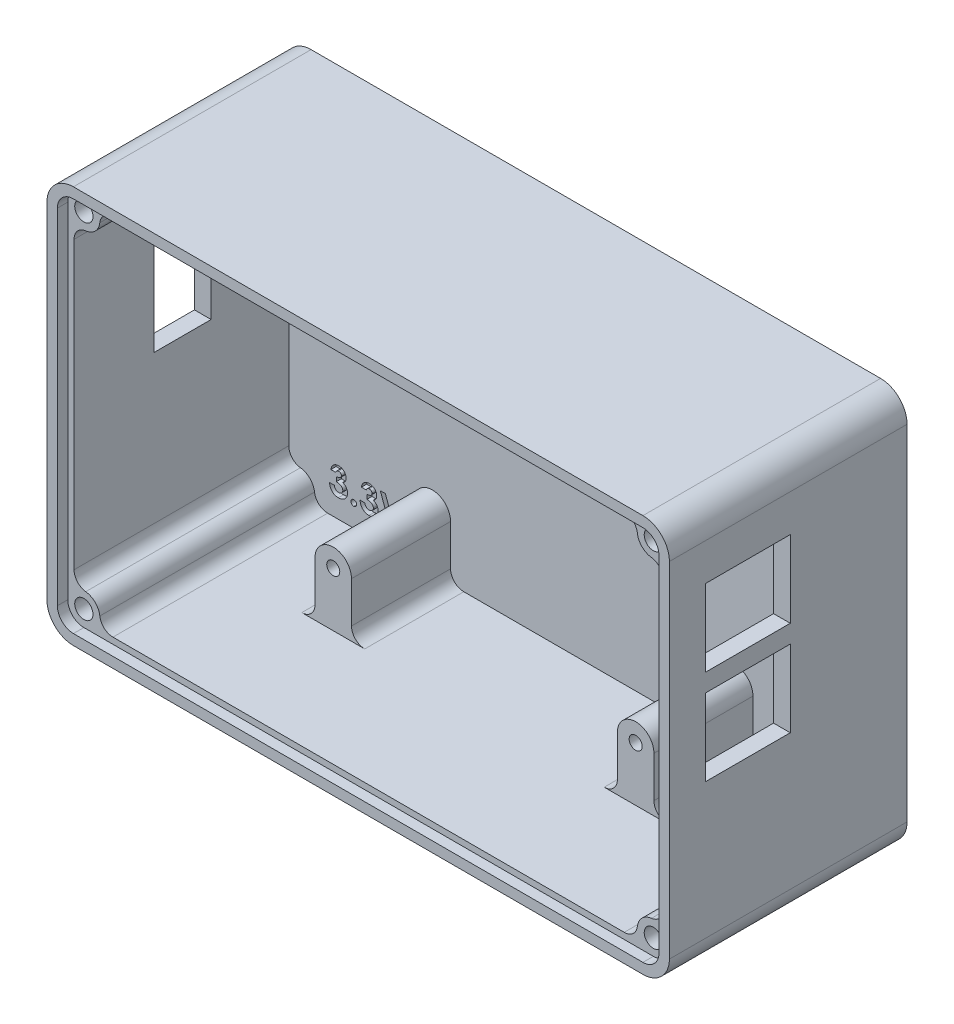
SolidWorks part; units mm, degrees
material "ABS"
ref_plane "Front Plane" through (0, 0, 0) normal (0, 0, 1) x (1, 0, 0)
ref_plane "Top Plane" through (0, 0, 0) normal (0, 1, 0) x (1, 0, 0)
ref_plane "Right Plane" through (0, 0, 0) normal (1, 0, 0) x (0, 0, -1)
sketch "OdroidOutline" plane through (0, 0, 0) normal (0, 0, 1) x (1, 0, 0)
  line L1 (-42.5, 28) -> (42.5, 28)
  line L2 (-42.5, 28) -> (-42.5, -28)
  line L3 (-42.5, -28) -> (42.5, -28)
  line L4 (42.5, 28) -> (42.5, -28)
  line L5 (-42.5, 28) -> (42.5, -28) construction
  line L6 (-42.5, -28) -> (42.5, 28) construction
  line L7 (19, -24.5) -> (-39, -24.5) construction
  line L8 (19, -24.5) -> (19, 24.5) construction
  line L9 (19, 24.5) -> (-39, 24.5) construction
  line L10 (-39, -24.5) -> (-39, 24.5) construction
  line L11 (44, -25.54) -> (22.3, -25.54)
  line L12 (44, -25.54) -> (44, -9.96)
  line L13 (44, -9.96) -> (22.3, -9.96)
  line L14 (22.3, -25.54) -> (22.3, -9.96)
  line L15 (44, -5.565) -> (26.44, -5.565)
  line L16 (44, -5.565) -> (44, 7.565)
  line L17 (44, 7.565) -> (26.44, 7.565)
  line L18 (26.44, -5.565) -> (26.44, 7.565)
  line L19 (44, 12.435) -> (26.44, 12.435)
  line L20 (44, 12.435) -> (44, 25.565)
  line L21 (44, 25.565) -> (26.44, 25.565)
  line L22 (26.44, 12.435) -> (26.44, 25.565)
  circle A0 centre (19, -24.5) radius 1.25
  circle A1 centre (-39, -24.5) radius 1.25
  circle A2 centre (-39, 24.5) radius 1.25
  circle A3 centre (19, 24.5) radius 1.25
  point P0 (0, 0)
  point P26 (44, -17.75)
  point P27 (44, 1)
  point P28 (44, 19)
  dimension "D7" = 2.5
  dimension "D1" = 85
  dimension "D2" = 56
  dimension "D3" = 58
  dimension "D4" = 49
  dimension "D5" = 3.5
  dimension "D6" = 3.5
  dimension "D8" = 10.25
  dimension "D9" = 29
  dimension "D10" = 47
  dimension "D11" = 15.58
  dimension "D12" = 21.7
  dimension "D13" = 13.13
  dimension "D14" = 17.56
  dimension "D15" = 1.5
sketch "BatteryOutline" plane through (0, 0, 0) normal (0, 0, 1) x (1, 0, 0)
  line L0 (6.5632, -21.195) -> (6.5632, 21.195) construction
  line L2 (-42.5, 0) -> (6.5632, 0) construction
  line L3 (-42.5, 28) -> (-42.5, -28) construction
  line L4 (6.5632, 21.195) -> (6.5632, 24.5) construction
  line L7 (44.3132, -30.5) -> (-31.1868, -30.5)
  line L8 (44.3132, -30.5) -> (44.3132, 30.5)
  line L9 (44.3132, 30.5) -> (-31.1868, 30.5)
  line L10 (-31.1868, -30.5) -> (-31.1868, 30.5)
  line L11 (44.3132, -30.5) -> (-31.1868, 30.5) construction
  line L12 (44.3132, 30.5) -> (-31.1868, -30.5) construction
  circle A0 centre (6.5632, 21.195) radius 1.75
  circle A1 centre (6.5632, -21.195) radius 1.75
  point P3 (6.5632, 0)
  dimension "D2" = 3.5
  dimension "D1" = 42.39
  dimension "D3" = 75.5
  dimension "D4" = 61
sketch "Sketch4" plane through (0, 0, 0) normal (0, 0, 1) x (1, 0, 0)
  line L0 (53.5, 0) -> (-53.5, 0) construction
  line L1 (53.5, -15) -> (53.5, 15) construction
  line L2 (-53.5, -15) -> (-53.5, 15) construction
  circle A0 centre (53.5, 15) radius 1.75
  circle A1 centre (-53.5, 15) radius 1.75
  circle A2 centre (-53.5, -15) radius 1.75
  circle A3 centre (53.5, -15) radius 1.75
  point P5 (0, 0)
  point P6 (53.5, 0)
  point P9 (-53.5, 0)
  dimension "D1" = 3.5
  dimension "D2" = 30
  dimension "D3" = 107
sketch "Sketch5" plane through (0, 0, 0) normal (0, 0, 1) x (1, 0, 0)
  line L0 (44.5696, 34.9) -> (-64.6504, 34.9)
  line L1 (44.5696, -38.1) -> (-64.6504, -38.1)
  line L2 (49.6496, -33.02) -> (49.6496, 33.02)
  line L3 (44.5696, 38.1) -> (-64.6504, 38.1)
  line L4 (-69.7304, -33.02) -> (-69.7304, 33.02)
  line L5 (49.6496, -38.1) -> (-69.7304, 38.1) construction
  line L6 (49.6496, 38.1) -> (-69.7304, -38.1) construction
  line L7 (-66.5304, -33.02) -> (-66.5304, 33.02)
  line L8 (44.5696, -34.9) -> (-64.6504, -34.9)
  line L9 (46.4496, -33.02) -> (46.4496, 33.02)
  arc A0 (-64.6504, -38.1) -> (-69.7304, -33.02) centre (-64.6504, -33.02) cw
  arc A1 (44.5696, -38.1) -> (49.6496, -33.02) centre (44.5696, -33.02) ccw
  arc A2 (49.6496, 33.02) -> (44.5696, 38.1) centre (44.5696, 33.02) ccw
  arc A3 (-64.6504, 38.1) -> (-69.7304, 33.02) centre (-64.6504, 33.02) ccw
  arc A4 (-64.6504, 34.9) -> (-66.5304, 33.02) centre (-64.6504, 33.02) ccw
  arc A5 (-64.6504, -34.9) -> (-66.5304, -33.02) centre (-64.6504, -33.02) cw
  arc A6 (44.5696, -34.9) -> (46.4496, -33.02) centre (44.5696, -33.02) ccw
  arc A7 (46.4496, 33.02) -> (44.5696, 34.9) centre (44.5696, 33.02) ccw
  dimension "D6" = 5.08
  dimension "D1" = 76.2
  dimension "D2" = 119.38
  dimension "D3" = 3.2
extrude "Enclosure Base" add sketch "Sketch5" along normal blind 2.4 contours L3 A3 L4 A0 L1 A1 L2 A2
extrude "Enclosure Wall" add sketch "Sketch5<3>" along normal blind 43.18 from surface contours L3 A3 L4 A0 L1 A1 L2 A2 A7 L9 A6 L8 A5 L7 A4 L0 region at (-10.0404, -36.6837, 0) starting at face at (-10.0404, 0, 2.4)
sketch "Sketch5<3>" plane through (0, 0, 0) normal (0, 0, 1) x (1, 0, 0) same geometry as "Sketch5"
sketch "Sketch6" plane through (0, 0, 2.4) normal (0, 0, 1) x (1, 0, 0)
  line L5 (-10, -24.5) -> (-10, 29.9225) construction
  line L6 (19, -24.5) -> (-39, -24.5) construction
  line L7 (-39, 0) -> (30.934, 0) construction
  line L8 (-39, -24.5) -> (-39, 24.5) construction
  line L19 (-35.5, 24.5) -> (-35.5, 34.9)
  line L20 (-64.6504, 34.9) -> (44.5696, 34.9) construction
  line L21 (-35.5, 34.9) -> (-42.5, 34.9)
  line L22 (-64.6504, 34.9) -> (44.5696, 34.9) construction
  line L23 (-42.5, 34.9) -> (-42.5, 24.5)
  line L24 (-42.5, 28) -> (42.5, 28) construction
  line L25 (15.5, 24.5) -> (15.5, 34.9)
  line L26 (15.5, 34.9) -> (22.5, 34.9)
  line L27 (22.5, 34.9) -> (22.5, 24.5)
  line L28 (15.5, -24.5) -> (15.5, -34.9)
  line L29 (15.5, -34.9) -> (22.5, -34.9)
  line L30 (22.5, -34.9) -> (22.5, -24.5)
  line L31 (-42.5, -34.9) -> (-42.5, -24.5)
  line L32 (-35.5, -34.9) -> (-42.5, -34.9)
  line L33 (-35.5, -24.5) -> (-35.5, -34.9)
  circle A4 centre (-39, 24.5) radius 1.25 construction
  circle A5 centre (-39, -24.5) radius 1.25 construction
  circle A6 centre (19, 24.5) radius 1.25 construction
  circle A7 centre (19, -24.5) radius 1.25 construction
  circle A8 centre (-39, 24.5) radius 1.25
  circle A9 centre (-39, -24.5) radius 1.25
  circle A10 centre (19, 24.5) radius 1.25
  circle A11 centre (19, -24.5) radius 1.25
  arc A12 (-42.5, 24.5) -> (-35.5, 24.5) centre (-39, 24.5) ccw
  arc A13 (15.5, 24.5) -> (22.5, 24.5) centre (19, 24.5) ccw
  arc A14 (-35.5, 24.5) -> (-42.5, 24.5) centre (-39, 24.5) ccw construction
  arc A15 (22.5, 24.5) -> (15.5, 24.5) centre (19, 24.5) ccw construction
  arc A16 (15.5, -24.5) -> (22.5, -24.5) centre (19, -24.5) cw
  arc A17 (-42.5, -24.5) -> (-35.5, -24.5) centre (-39, -24.5) cw
extrude "Odroid Mount Spacer" add sketch "Sketch6" along normal blind 19
sketch "Sketch7" plane through (-69.7304, 0, 0) normal (-1, 0, 0) x (0, 0, 1)
  line L1 (28.29, 0.9747) -> (17.29, 0.9747)
  line L2 (28.29, 0.9747) -> (28.29, 26.9747)
  line L3 (28.29, 26.9747) -> (17.29, 26.9747)
  line L4 (17.29, 0.9747) -> (17.29, 26.9747)
  line L5 (28.29, 0.9747) -> (17.29, 26.9747) construction
  line L6 (28.29, 26.9747) -> (17.29, 0.9747) construction
  line L7 (22.79, 33.02) -> (22.79, 13.9747) construction
  line L8 (45.58, 33.02) -> (0, 33.02) construction
  point P0 (22.79, 13.9747)
  dimension "D1" = 26
  dimension "D2" = 11
extrude "Power Switch Hole" cut sketch "Sketch7" against normal blind 7.112
sketch "Sketch8" plane through (0, 0, 2.4) normal (0, 0, 1) x (1, 0, 0)
  line L0 (-58.9104, 25.9564) -> (-58.9104, -31.1936) construction
  line L1 (-66.5304, -33.02) -> (-66.5304, 33.02) construction
  line L4 (49.6496, 38.1) -> (-69.7304, -38.1) construction
  text T0 "<b>3.3V</b>" font "Century Gothic" height 5.08
  text T1 "<b>5.0V</b>" font "Century Gothic" height 5.08
  text T2 "<b>Vin</b>" font "Century Gothic" height 3.175
  dimension "D1" = 57.15
  dimension "D2" = 7.62
extrude "Labeling" cut sketch "Sketch8" against normal blind 1
sketch "Sketch9" plane through (0, 0, 45.58) normal (0, 0, 1) x (1, 0, 0)
  line L0 (44.5696, 34.9) -> (-64.6504, 34.9) construction
  line L1 (46.4496, -33.02) -> (46.4496, 33.02) construction
  line L2 (44.5696, -34.9) -> (-64.6504, -34.9) construction
  line L3 (-66.5304, -33.02) -> (-66.5304, 33.02) construction
  line L4 (46.4496, -33.02) -> (46.4496, 33.02)
  line L5 (44.5696, -34.9) -> (-64.6504, -34.9)
  line L6 (-66.5304, -33.02) -> (-66.5304, 33.02)
  line L7 (44.5696, 34.9) -> (-64.6504, 34.9)
  line L8 (44.5696, 36.1) -> (-64.6504, 36.1)
  line L9 (-67.7304, 33.02) -> (-67.7304, -33.02)
  line L10 (-64.6504, -36.1) -> (44.5696, -36.1)
  line L11 (47.6496, -33.02) -> (47.6496, 33.02)
  line L12 (44.5696, 36.1) -> (-64.6504, 36.1)
  line L13 (-67.7304, 33.02) -> (-67.7304, -33.02)
  line L14 (-64.6504, -36.1) -> (44.5696, -36.1)
  line L15 (47.6496, -33.02) -> (47.6496, 33.02)
  arc A0 (46.4496, 33.02) -> (44.5696, 34.9) centre (44.5696, 33.02) ccw construction
  arc A1 (44.5696, -34.9) -> (46.4496, -33.02) centre (44.5696, -33.02) ccw construction
  arc A2 (-66.5304, -33.02) -> (-64.6504, -34.9) centre (-64.6504, -33.02) ccw construction
  arc A3 (-64.6504, 34.9) -> (-66.5304, 33.02) centre (-64.6504, 33.02) ccw construction
  arc A4 (46.4496, 33.02) -> (44.5696, 34.9) centre (44.5696, 33.02) ccw
  arc A5 (44.5696, -34.9) -> (46.4496, -33.02) centre (44.5696, -33.02) ccw
  arc A6 (-66.5304, -33.02) -> (-64.6504, -34.9) centre (-64.6504, -33.02) ccw
  arc A7 (-64.6504, 34.9) -> (-66.5304, 33.02) centre (-64.6504, 33.02) ccw
  arc A8 (47.6496, 33.02) -> (44.5696, 36.1) centre (44.5696, 33.02) ccw
  arc A9 (-64.6504, 36.1) -> (-67.7304, 33.02) centre (-64.6504, 33.02) ccw
  arc A10 (-67.7304, -33.02) -> (-64.6504, -36.1) centre (-64.6504, -33.02) ccw
  arc A11 (44.5696, -36.1) -> (47.6496, -33.02) centre (44.5696, -33.02) ccw
  arc A12 (47.6496, 33.02) -> (44.5696, 36.1) centre (44.5696, 33.02) ccw
  arc A13 (-64.6504, 36.1) -> (-67.7304, 33.02) centre (-64.6504, 33.02) ccw
  arc A14 (-67.7304, -33.02) -> (-64.6504, -36.1) centre (-64.6504, -33.02) ccw
  arc A15 (44.5696, -36.1) -> (47.6496, -33.02) centre (44.5696, -33.02) ccw
extrude "Top Cover Groove" cut sketch "Sketch9" against normal blind 2
sketch "Sketch10" plane through (0, 0, 0) normal (0, 0, 1) x (1, 0, 0)
  circle A0 centre (-64.6504, 33.02) radius 3.08
  circle A1 centre (-64.6504, -33.02) radius 3.08
  circle A2 centre (44.5696, 33.02) radius 3.08
  circle A3 centre (44.5696, -33.02) radius 3.08
  arc A4 (47.6496, 33.02) -> (44.5696, 36.1) centre (44.5696, 33.02) ccw construction
  arc A5 (-64.6504, 36.1) -> (-67.7304, 33.02) centre (-64.6504, 33.02) ccw construction
  arc A6 (-67.7304, -33.02) -> (-64.6504, -36.1) centre (-64.6504, -33.02) ccw construction
  arc A7 (44.5696, -36.1) -> (47.6496, -33.02) centre (44.5696, -33.02) ccw construction
  circle A8 centre (-64.6504, 33.02) radius 1.75
  circle A9 centre (-64.6504, -33.02) radius 1.75
  circle A10 centre (44.5696, -33.02) radius 1.75
  circle A11 centre (44.5696, 33.02) radius 1.75
  dimension "D1" = 3.5
extrude "Boss-Extrude4" add sketch "Sketch10" along normal up to surface (43.58 mm away) up to face at (-10.0404, 0, 43.58)
fillet "Fillet1" radius 2.54 8 edges at (46.4496, 30.5803, 22.99) (42.1299, 34.9, 22.99) (-62.2107, 34.9, 22.99) (-66.5304, 30.5803, 22.99) (-66.5304, -30.5803, 22.99) (-62.2107, -34.9, 22.99) (42.1299, -34.9, 22.99) (46.4496, -30.5803, 22.99)
sketch "Sketch11" plane through (0, 0, 2.4) normal (0, 0, 1) x (1, 0, 0)
  line L1 (21.3865, 7.3925) -> (-1.1635, 7.3925)
  line L2 (21.3865, 7.3925) -> (21.3865, 24.6925)
  line L3 (21.3865, 24.6925) -> (-1.1635, 24.6925)
  line L4 (-1.1635, 7.3925) -> (-1.1635, 24.6925)
  line L5 (21.3865, 7.3925) -> (-1.1635, 24.6925) construction
  line L6 (21.3865, 24.6925) -> (-1.1635, 7.3925) construction
  point P0 (10.1115, 16.0425)
  dimension "D1" = 17.3
  dimension "D2" = 22.55
ref_plane "Plane2" through (0, 0, 38.4) normal (0, 0, 1) x (1, 0, 0)
sketch "Sketch12" plane through (0, 0, 0) normal (0, 0, -1) x (-1, 0, 0)
  line L0 (5.7994, -38.1) -> (5.7994, -46.1)
  line L1 (-44.5696, -38.1) -> (64.6504, -38.1) construction
  line L2 (5.7994, -46.1) -> (-4.2006, -46.1)
  line L3 (-4.2006, -46.1) -> (-4.2006, -38.1)
  line L4 (5.7994, -38.1) -> (-4.2006, -38.1)
  dimension "D1" = 8
  dimension "D2" = 10
extrude "Boss-Extrude5" [suppressed] add sketch "Sketch12" against normal up to surface (45.58 mm away)
sketch "Sketch15" plane through (0, 0, 2.4) normal (0, 0, 1) x (1, 0, 0)
  line L1 (-100.2631, 17.9297) -> (-79.2631, 17.9297) construction
  line L2 (-100.2631, 17.9297) -> (-100.2631, -24.0703) construction
  line L3 (-100.2631, -24.0703) -> (-79.2631, -24.0703) construction
  line L4 (-79.2631, 17.9297) -> (-79.2631, -24.0703) construction
  dimension "D1" = 21
  dimension "D2" = 42
sketch "Sketch16" [suppressed] plane through (0, -46.1, 0) normal (0, -1, 0) x (1, 0, 0)
  line L0 (-0.7994, 40.58) -> (-0.7994, 5.2274) construction
  line L1 (4.2006, 45.58) -> (-5.7994, 45.58) construction
  line L2 (-0.7994, 40.58) -> (-0.7994, 45.58) construction
  circle A0 centre (-0.7994, 40.58) radius 1.75
  circle A1 centre (-0.7994, 5.2274) radius 1.75
  dimension "D1" = 3.5
  dimension "D2" = 5
extrude "Cut-Extrude1" [suppressed] cut sketch "Sketch16" against normal up to surface (8 mm away)
fillet "Fillet2" radius 2.54 8 edges at (22.5, -34.9, 11.9) (15.5, -34.9, 11.9) (-35.5, -34.9, 11.9) (-42.5, -34.9, 11.9) (-42.5, 34.9, 11.9) (15.5, 34.9, 11.9) (22.5, 34.9, 11.9) (-35.5, 34.9, 11.9)
sketch "Sketch17" plane through (49.6496, 0, 0) normal (1, 0, 0) x (0, 0, -1)
  line L0 (-36.506, 8.962) -> (-36.506, 8.312) construction
  line L1 (-36.506, 8.312) -> (-31.506, 8.312) construction
  line L2 (-31.506, 8.312) -> (-31.506, 8.962) construction
  line L3 (-28.506, 8.962) -> (-28.506, 8.312) construction
  line L4 (-28.506, 8.312) -> (-23.506, 8.312) construction
  line L5 (-23.506, 8.312) -> (-23.506, 8.962) construction
  line L6 (-31.256, 8.962) -> (-29.256, 8.962) construction
  line L7 (-29.256, 22.212) -> (-31.256, 22.212) construction
  line L8 (-28.506, 22.212) -> (-29.256, 22.212) construction
  line L9 (-29.256, 8.962) -> (-28.506, 8.962) construction
  line L10 (-23.506, 8.962) -> (-22.4, 8.962) construction
  line L11 (-22.4, 8.962) -> (-22.4, 22.212) construction
  line L12 (-22.4, 22.212) -> (-23.506, 22.212) construction
  line L13 (-23.506, 22.862) -> (-28.506, 22.862) construction
  line L14 (-28.506, 22.862) -> (-28.506, 22.212) construction
  line L15 (-23.506, 22.212) -> (-23.506, 22.862) construction
  line L16 (-38.006, 21.462) -> (-38.656, 21.462) construction
  line L17 (-38.656, 21.462) -> (-38.656, 9.962) construction
  line L18 (-38.656, 9.962) -> (-38.006, 9.962) construction
  line L19 (-36.506, 22.212) -> (-38.006, 22.212) construction
  line L20 (-38.006, 22.212) -> (-38.006, 21.462) construction
  line L21 (-38.006, 9.962) -> (-38.006, 8.962) construction
  line L22 (-38.006, 8.962) -> (-36.506, 8.962) construction
  line L23 (-31.506, 8.962) -> (-31.256, 8.962) construction
  line L24 (-31.256, 22.212) -> (-31.506, 22.212) construction
  line L25 (-31.506, 22.862) -> (-36.506, 22.862) construction
  line L26 (-36.506, 22.862) -> (-36.506, 22.212) construction
  line L27 (-31.506, 22.212) -> (-31.506, 22.862) construction
  line L56 (-21.4, 25.75) -> (-21.4, 23.25) construction
  line L57 (-22.4, 11.168) -> (-38.656, 11.168)
  line L58 (-22.4, 11.168) -> (-22.4, 25.9)
  line L59 (-22.4, 25.9) -> (-38.656, 25.9)
  line L60 (-38.656, 11.168) -> (-38.656, 25.9)
  line L61 (-38.656, 7.718) -> (-22.4, 7.718)
  line L62 (-38.656, 7.718) -> (-38.656, -7.014)
  line L63 (-38.656, -7.014) -> (-22.4, -7.014)
  line L64 (-22.4, 7.718) -> (-22.4, -7.014)
  line L65 (-21.4, 25.75) -> (-21.4, 23.25)
  point P19 (-21.4, 24.5)
  dimension "D2" = 14.732
  dimension "D4" = 16.256
  dimension "D1" = 3.45
  dimension "D5" = 1
  dimension "D3" = 1.4
extrude "Cut-Extrude2" cut sketch "Sketch17" against normal up to next contours L64 L61 L62 L63 | L60 L57 L58 L59 region at (49.6496, 18.534, 30.528) region at (49.6496, 0.352, 30.528)
equation "\"D1@OdroidOutline\"=85mm"
equation "\"D2@OdroidOutline\"=56mm"
equation "\"D3@OdroidOutline\"=58mm"
equation "\"D4@OdroidOutline\"=49mm"
equation "\"D5@OdroidOutline\"=3.5mm"
equation "\"D6@OdroidOutline\"=3.5mm"
equation "\"D7@OdroidOutline\"=2.5mm"
equation "\"D9@OdroidOutline\"=29mm"
equation "\"D10@OdroidOutline\"=47mm"
equation "\"D11@OdroidOutline\"=15.58mm"
equation "\"D13@OdroidOutline\"=13.13mm"
equation "\"D15@OdroidOutline\"=1.5mm"
equation "\"D1@BatteryOutline\" = 42.39mm"
equation "\"D2@BatteryOutline\" = 3.5mm"
equation "\"D1@Sketch4\"=3.5mm"
equation "\"D2@Sketch4\"=30mm"
equation "\"D3@Sketch4\"=107mm"
equation "\"D3@Sketch5\"=3.2mm"
equation "\"D1@Enclosure Base\" = 2.4mm"
equation "\"D1@Enclosure Wall\"=1.7in"
equation "\"D1@Odroid Mount Spacer\"=19mm"
equation "\"D4@BatteryOutline\" = 61mm"
equation "\"D1@Sketch7\"=26mm"
equation "\"D2@Sketch7\"=11mm"
equation "\"D1@Labeling\" = 1mm"
equation "\"D1@Sketch9\"=2mm"
equation "\"D1@Top Cover Groove\" = 2mm"
equation "\"D1@Sketch10\"=3.50mm"
equation "\"D1@Sketch11\"=17.3mm"
equation "\"D2@Sketch11\"=22.55mm"
equation "\"D1\"= 3.6mm"
equation "\"D1\"= 20mm"
equation "\"D1@Sketch12\"=8mm"
equation "\"D2@Sketch12\"=10mm"
equation "\"D1@Sketch15\"=21mm"
equation "\"D2@Sketch15\"=42mm"
equation "\"D1@Sketch16\"=3.5mm"
equation "\"D2@Sketch16\"=5mm"
equation "\"D1\"= 8mm"
equation "\"D1@Sketch17\"=3.45mm"
equation "\"D5@Sketch17\"=1mm"
equation "\"D3@Sketch17\"=1.4mm"
